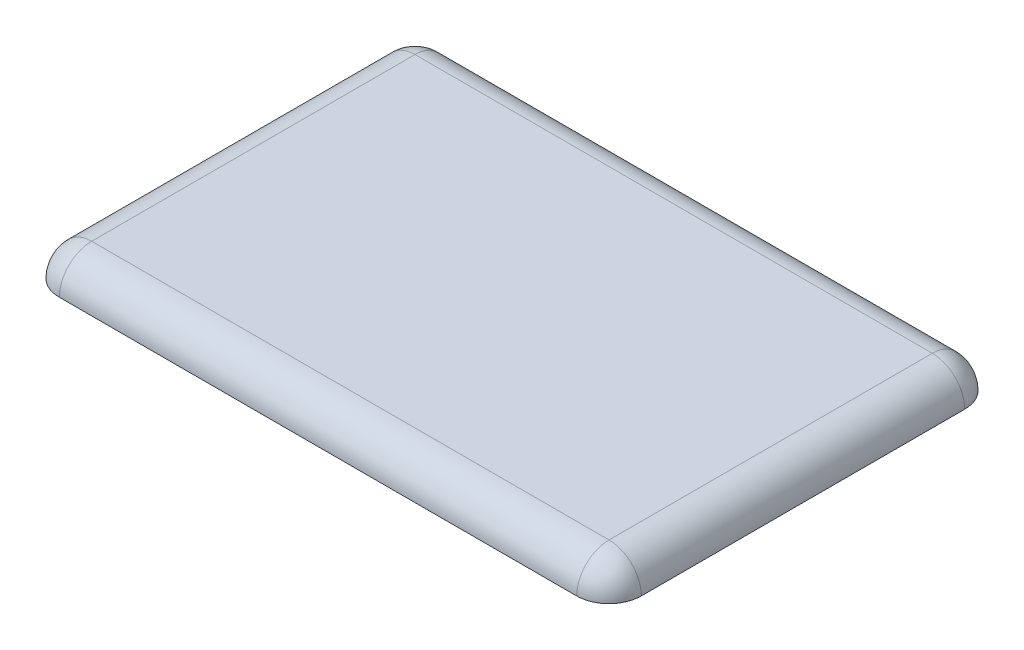
SolidWorks part; units mm, degrees
ref_plane "Front Plane" through (0, 0, 0) normal (0, 0, 1) x (1, 0, 0)
ref_plane "Top Plane" through (0, 0, 0) normal (0, 1, 0) x (1, 0, 0)
ref_plane "Right Plane" through (0, 0, 0) normal (1, 0, 0) x (0, 0, -1)
sketch "Sketch1" plane through (0, 0, 0) normal (0, 1, 0) x (1, 0, 0)
  line L1 (-228.6, -152.4) -> (228.6, -152.4)
  line L2 (-228.6, -152.4) -> (-228.6, 152.4)
  line L3 (-228.6, 152.4) -> (228.6, 152.4)
  line L4 (228.6, -152.4) -> (228.6, 152.4)
  line L5 (-228.6, -152.4) -> (228.6, 152.4) construction
  line L6 (-228.6, 152.4) -> (228.6, -152.4) construction
  point P0 (0, 0)
  dimension "D1" = 457.2
  dimension "D2" = 304.8
extrude "Boss-Extrude1" add sketch "Sketch1" along normal blind 25.4
fillet "Fillet2" radius 25.4 4 edges at (228.6, 12.7, -152.4) (228.6, 12.7, 152.4) (-228.6, 12.7, 152.4) (-228.6, 12.7, -152.4)
fillet "Fillet3" radius 25.4 4 edges at (228.6, 25.4, 0) (0, 25.4, -152.4) (-228.6, 25.4, 0) (0, 25.4, 152.4) type face fillet first side face at (0, 25.4, 0) second side face at (228.6, 12.7, 0) second side face at (0, 12.7, 152.4) second side face at (-228.6, 12.7, 0) second side face at (0, 12.7, -152.4)
